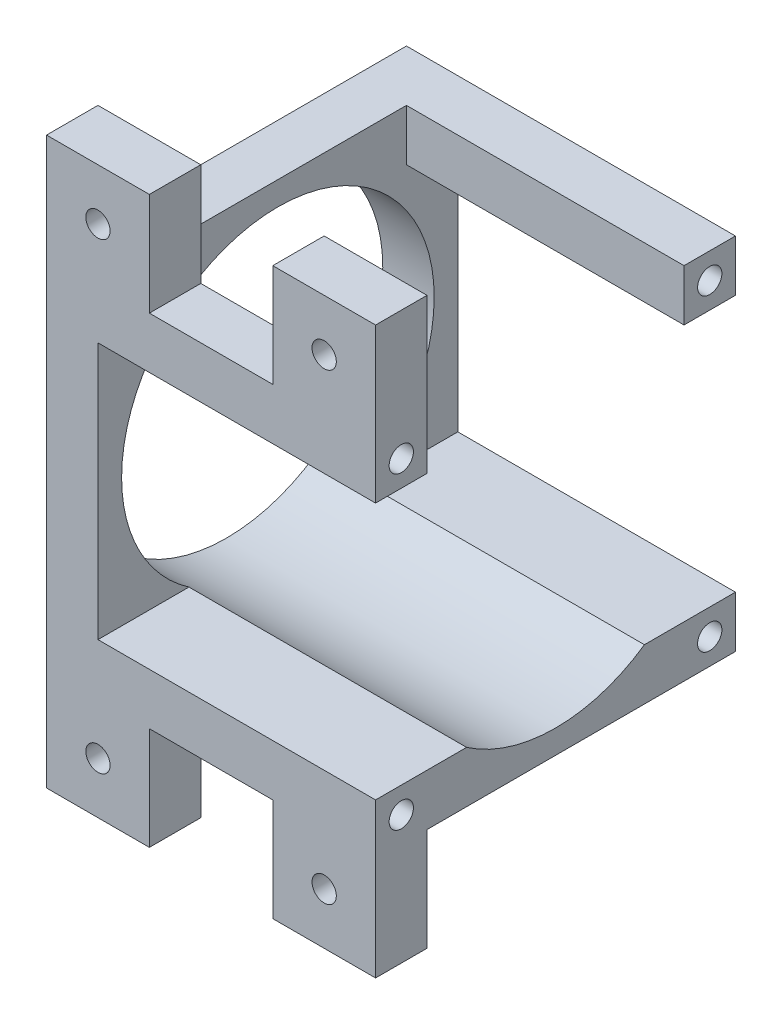
SolidWorks part; units mm, degrees
ref_plane "Front Plane" through (0, 0, 0) normal (0, 0, 1) x (1, 0, 0)
ref_plane "Top Plane" through (0, 0, 0) normal (0, 1, 0) x (1, 0, 0)
ref_plane "Right Plane" through (0, 0, 0) normal (1, 0, 0) x (0, 0, -1)
sketch "Sketch1" plane through (0, 0, 0) normal (0, 1, 0) x (1, 0, 0)
  line L1 (0, 0) -> (40.64, 0)
  line L2 (0, 0) -> (0, 44.45)
  line L3 (0, 44.45) -> (40.64, 44.45)
  line L4 (40.64, 0) -> (40.64, 44.45)
  dimension "D1" = 40.64
  dimension "D2" = 44.45
extrude "Boss-Extrude1" add sketch "Sketch1" along normal blind 44.45
sketch "Sketch4" plane through (0, 0, 0) normal (-1, 0, 0) x (0, 0, 1)
  line L1 (-44.45, 44.45) -> (-44.45, 0) construction
  line L3 (-44.45, 44.45) -> (0, 44.45) construction
  circle A0 centre (-22.225, 22.225) radius 19.304
  dimension "D1" = 38.608
  dimension "D2" = 22.225
  dimension "D3" = 22.225
extrude "Cut-Extrude3" cut sketch "Sketch4" against normal through all contours A0
sketch "Sketch5" plane through (0, 0, -44.45) normal (0, 0, -1) x (-1, 0, 0)
  line L0 (0, 44.45) -> (-40.64, 44.45) construction
  line L1 (-6.35, 44.45) -> (-40.64, 44.45)
  line L2 (-6.35, 44.45) -> (-6.35, 6.35)
  line L3 (-6.35, 6.35) -> (-40.64, 6.35)
  line L4 (-40.64, 44.45) -> (-40.64, 6.35)
  line L5 (-40.64, 44.45) -> (-40.64, 0) construction
  dimension "D1" = 34.29
  dimension "D2" = 38.1
extrude "Cut-Extrude4" cut sketch "Sketch5" against normal through all contours L2 L3 L4 L1
sketch "Sketch6" plane through (6.35, 0, 0) normal (1, 0, 0) x (0, 0, -1)
  line L1 (0, 44.45) -> (6.35, 44.45)
  line L2 (0, 44.45) -> (0, 38.1)
  line L3 (0, 38.1) -> (6.35, 38.1)
  line L4 (6.35, 44.45) -> (6.35, 38.1)
  line L5 (44.45, 44.45) -> (38.1, 44.45)
  line L6 (44.45, 44.45) -> (44.45, 38.1)
  line L7 (44.45, 38.1) -> (38.1, 38.1)
  line L8 (38.1, 44.45) -> (38.1, 38.1)
  dimension "D1" = 6.35
  dimension "D2" = 6.35
  dimension "D3" = 6.35
  dimension "D4" = 6.35
extrude "Boss-Extrude2" add sketch "Sketch6" along normal blind 34.29
sketch "Sketch7" plane through (40.64, 0, 0) normal (1, 0, 0) x (0, 0, -1)
  line L0 (6.35, 44.45) -> (0, 44.45) construction
  line L3 (0, 44.45) -> (0, 38.1) construction
  line L4 (44.45, 44.45) -> (38.1, 44.45) construction
  line L5 (38.1, 44.45) -> (38.1, 38.1) construction
  line L6 (33.2081, 6.35) -> (44.45, 6.35) construction
  line L8 (44.45, 6.35) -> (44.45, 0) construction
  line L9 (0, 6.35) -> (0, 0) construction
  line L11 (0, 0) -> (44.45, 0) construction
  circle A0 centre (3.175, 41.275) radius 1.5
  circle A1 centre (41.275, 41.275) radius 1.5
  circle A2 centre (41.275, 3.175) radius 1.5
  circle A3 centre (3.175, 3.175) radius 1.5
  point P14 (41.275, 44.45)
  dimension "D1" = 3
  dimension "D2" = 3
  dimension "D3" = 3
  dimension "D4" = 3
  dimension "D5" = 3.175
  dimension "D6" = 3.175
  dimension "D7" = 3.175
  dimension "D8" = 3.175
  dimension "D9" = 3.175
  dimension "D10" = 3.175
  dimension "D11" = 3.175
  dimension "D12" = 3.175
extrude "Cut-Extrude5" cut sketch "Sketch7" against normal blind 6.35
sketch "Sketch8" plane through (0, 44.45, 0) normal (0, 1, 0) x (1, 0, 0)
  line L0 (40.64, 6.35) -> (6.35, 6.35) construction
  line L1 (0, 0) -> (12.7, 0)
  line L2 (0, 0) -> (0, 6.35)
  line L3 (0, 6.35) -> (12.7, 6.35)
  line L4 (12.7, 0) -> (12.7, 6.35)
  line L6 (40.64, 0) -> (27.94, 0)
  line L7 (40.64, 0) -> (40.64, 6.35)
  line L8 (40.64, 6.35) -> (27.94, 6.35)
  line L9 (27.94, 0) -> (27.94, 6.35)
  dimension "D1" = 12.7
  dimension "D2" = 12.7
extrude "Boss-Extrude3" add sketch "Sketch8" along normal blind 12.7
sketch "Sketch9" plane through (0, 0, -6.35) normal (0, 0, -1) x (-1, 0, 0)
  line L0 (0, 57.15) -> (0, 44.45) construction
  line L1 (-12.7, 57.15) -> (0, 57.15) construction
  line L2 (-27.94, 57.15) -> (-27.94, 44.45) construction
  line L3 (-40.64, 57.15) -> (-27.94, 57.15) construction
  circle A0 centre (-6.35, 50.8) radius 1.5
  circle A1 centre (-34.29, 50.8) radius 1.5
  point P10 (-34.29, 57.15)
  point P12 (0, 0)
  dimension "D1" = 3
  dimension "D2" = 3
  dimension "D3" = 6.35
  dimension "D4" = 6.35
  dimension "D5" = 6.35
  dimension "D6" = 6.35
extrude "Cut-Extrude6" cut sketch "Sketch9" against normal blind 12.7
pattern_linear "LPattern1" count 2 spacing 57.15 along (0, -1, 0) of "Cut-Extrude6", "Boss-Extrude3"
